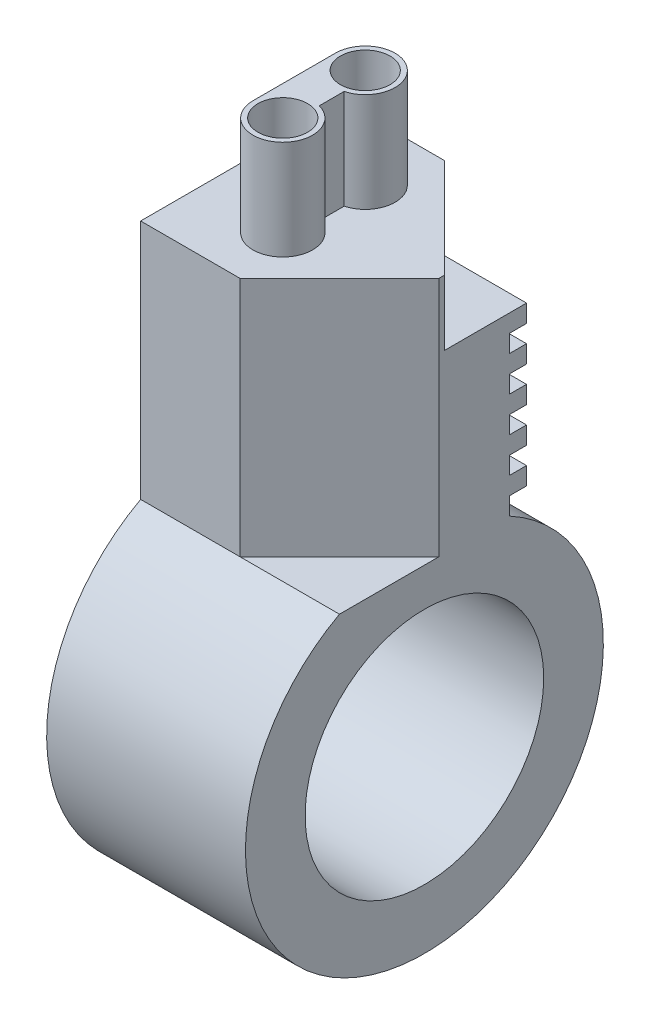
SolidWorks part; units mm, degrees
ref_plane "Front Plane" through (0, 0, 0) normal (0, 0, 1) x (1, 0, 0)
ref_plane "Top Plane" through (0, 0, 0) normal (0, 1, 0) x (1, 0, 0)
ref_plane "Right Plane" through (0, 0, 0) normal (1, 0, 0) x (0, 0, -1)
sketch "Sketch1" plane through (0, 0, 0) normal (1, 0, 0) x (0, 0, -1)
  line L0 (-4.2732, 7.9209) -> (-4.2732, 20.0485)
  line L1 (-4.2732, 20.0485) -> (6, 20.0485)
  line L2 (6, 20.0485) -> (6, 17.6493)
  line L3 (6, 17.6493) -> (4.2732, 17.6493)
  line L5 (4.2732, 17.6493) -> (4.2732, 16.768)
  line L6 (4.2732, 16.768) -> (5.1366, 16.768)
  line L8 (5.1366, 14.1105) -> (4.2732, 14.1105)
  line L9 (4.2732, 14.1105) -> (4.2732, 13.2291)
  line L10 (4.2732, 13.2291) -> (5.1366, 13.2291)
  line L11 (5.1366, 13.2291) -> (5.1366, 12.341)
  line L12 (5.1366, 12.341) -> (4.2732, 12.341)
  line L13 (4.2732, 12.341) -> (4.2732, 11.4597)
  line L14 (4.2732, 11.4597) -> (5.1366, 11.4597)
  line L15 (5.1366, 11.4597) -> (5.1366, 10.5716)
  line L16 (5.1366, 10.5716) -> (4.2732, 10.5716)
  line L17 (4.2732, 10.5716) -> (4.2732, 9.6903)
  line L18 (4.2732, 9.6903) -> (5.1366, 9.6903)
  line L19 (5.1366, 9.6903) -> (5.1366, 8.8022)
  line L20 (5.1366, 8.8022) -> (4.2732, 8.8022)
  line L21 (4.2732, 8.8022) -> (4.2732, 7.9209)
  line L22 (5.1366, 16.768) -> (5.1366, 15.8799)
  line L23 (5.1366, 15.8799) -> (4.2732, 15.8799)
  line L24 (4.2732, 15.8799) -> (4.2732, 14.9986)
  line L25 (4.2732, 14.9986) -> (5.1366, 14.9986)
  line L26 (5.1366, 14.9986) -> (5.1366, 14.1105)
  circle A0 centre (0, 0) radius 6
  arc A2 (-4.2732, 7.9209) -> (4.2732, 7.9209) centre (0, 0) ccw
  circle A3 centre (0, 0) radius 9 construction
  point P4 (5.1366, 17.6493)
  dimension "D1" = 12
  dimension "D2" = 3
extrude "Boss-Extrude1" add sketch "Sketch1" along normal blind 10
sketch "Sketch2" plane through (0, 20.0485, 0) normal (0, 1, 0) x (1, 0, 0)
  line L1 (10, -4.2732) -> (0, -4.2732) construction
  line L2 (10, 6) -> (0, 6) construction
  line L4 (5, 6) -> (10, 1)
  line L5 (10, 6) -> (10, -4.2732) construction
  line L6 (10, 1) -> (10, 6)
  line L7 (10, 6) -> (5, 6)
  line L8 (10, -4.2732) -> (5, -4.2732)
  line L9 (10, -4.2732) -> (0, -4.2732) construction
  line L10 (5, -4.2732) -> (10, 0.7268)
  line L11 (10, 0.7268) -> (10, -4.2732)
  line L12 (2.5869, 2.9368) -> (2.5869, -1.21)
  line L13 (4.4752, 1.488) -> (4.4752, 0.2389)
  line L14 (0, 6) -> (0, -4.2732) construction
  arc A2 (4.4752, 1.488) -> (2.5869, 2.9368) centre (4.0869, 2.9368) ccw
  arc A3 (2.5869, -1.21) -> (4.4752, 0.2389) centre (4.0869, -1.21) ccw
  point P1 (5, 4.1269)
  point P8 (5, -4.2732)
  point P11 (5, 6)
  point P23 (2.5869, 0.8634)
  point P28 (0, 0.8634)
  line M4 (0, -4.2732) -> (10, -4.2732)
  line M5 (10, -4.2732) -> (10, 6)
  line M6 (10, 6) -> (0, 6)
  dimension "D1" = 3
  dimension "D2" = 3
extrude "Cut-Extrude1" cut sketch "Sketch2" against normal up to surface (3.2804 mm away) contours L4 M6 M5 | L10 M4 M5 region at (8.3333, 20.0485, -4.3333) region at (8.3333, 20.0485, 2.6065) up to face at (5, 16.768, -4.7049)
extrude "Cut-Extrude2" cut sketch "Sketch2<5>" against normal up to vertex (12.1276 mm away) contours L10 M4 M5 region at (8.3333, 20.0485, 2.6065) up to point (0, 7.9209, 4.2732)
sketch "Sketch2<5>" plane through (0, 20.0485, 0) normal (0, 1, 0) x (1, 0, 0) same geometry as "Sketch2"
extrude "Boss-Extrude7" add sketch "Sketch2<6>" along normal blind 5 contours L12 A3 L13 A2 region at (3.9524, 20.0485, -0.8634)
sketch "Sketch2<6>" plane through (0, 20.0485, 0) normal (0, 1, 0) x (1, 0, 0) same geometry as "Sketch2"
sketch "Sketch3" plane through (0, 25.0485, 0) normal (0, 1, 0) x (1, 0, 0)
  circle A0 centre (4.0869, 2.9368) radius 1.25
  circle A1 centre (4.0869, -1.21) radius 1.25
  arc A2 (4.4752, 1.488) -> (2.5869, 2.9368) centre (4.0869, 2.9368) ccw construction
  arc A3 (2.5869, -1.21) -> (4.4752, 0.2389) centre (4.0869, -1.21) ccw construction
  dimension "D1" = 2.5
  dimension "D2" = 2.5
extrude "Cut-Extrude3" cut sketch "Sketch3" against normal up to surface (5 mm away) up to face at (4.2655, 20.0485, -0.8634)
extrude "Cut-Extrude4" cut sketch "Sketch3<2>" against normal up to surface (11.8193 mm away) up to face at (5, 13.2291, -4.7049)
sketch "Sketch3<2>" plane through (0, 25.0485, 0) normal (0, 1, 0) x (1, 0, 0) same geometry as "Sketch3"
